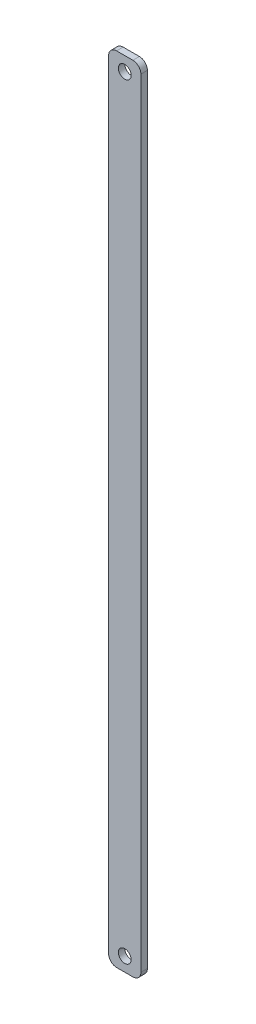
SolidWorks part; units mm, degrees
material "5052-H32"
ref_plane "Front Plane" through (0, 0, 0) normal (0, 0, 1) x (1, 0, 0)
ref_plane "Top Plane" through (0, 0, 0) normal (0, 1, 0) x (1, 0, 0)
ref_plane "Right Plane" through (0, 0, 0) normal (1, 0, 0) x (0, 0, -1)
sketch "Sketch1" plane through (0, 0, 0) normal (0, 1, 0) x (1, 0, 0)
  line L1 (-4.035, -0.815) -> (4.035, -0.815)
  line L2 (-4.035, -0.815) -> (-4.035, 0.815)
  line L3 (-4.035, 0.815) -> (4.035, 0.815)
  line L4 (4.035, -0.815) -> (4.035, 0.815)
  line L5 (-4.035, -0.815) -> (4.035, 0.815) construction
  line L6 (-4.035, 0.815) -> (4.035, -0.815) construction
  point P0 (0, 0)
  dimension "D1" = 8.07
  dimension "D2" = 1.63
extrude "Boss-Extrude1" add sketch "Sketch1" along normal blind 198.37
sketch "Sketch2" plane through (0, 0, 0.815) normal (0, 0, 1) x (1, 0, 0)
  line L0 (-4.035, 198.37) -> (-4.035, 0) construction
  line L1 (-4.035, 198.37) -> (4.035, 198.37) construction
  line L3 (4.035, 198.37) -> (4.035, 0) construction
  circle A0 centre (-0.005, 3.5) radius 1.6
  circle A1 centre (0.005, 194.87) radius 1.6
  dimension "D2" = 3.2
  dimension "D4" = 3.2
  dimension "D1" = 3.5
  dimension "D3" = 4.03
  dimension "D5" = 3.5
  dimension "D6" = 4.03
extrude "Cut-Extrude1" cut sketch "Sketch2" against normal up to surface (1.63 mm away) up to face at (0, 99.185, -0.815)
fillet "Fillet1" radius 2 4 edges at (-4.035, 0, 0) (4.035, 0, 0) (-4.035, 198.37, 0) (4.035, 198.37, 0)
equation "\"D6@Sketch2\"=\"D3@Sketch2\""
equation "\"D4@Sketch2\"=\"D2@Sketch2\""
